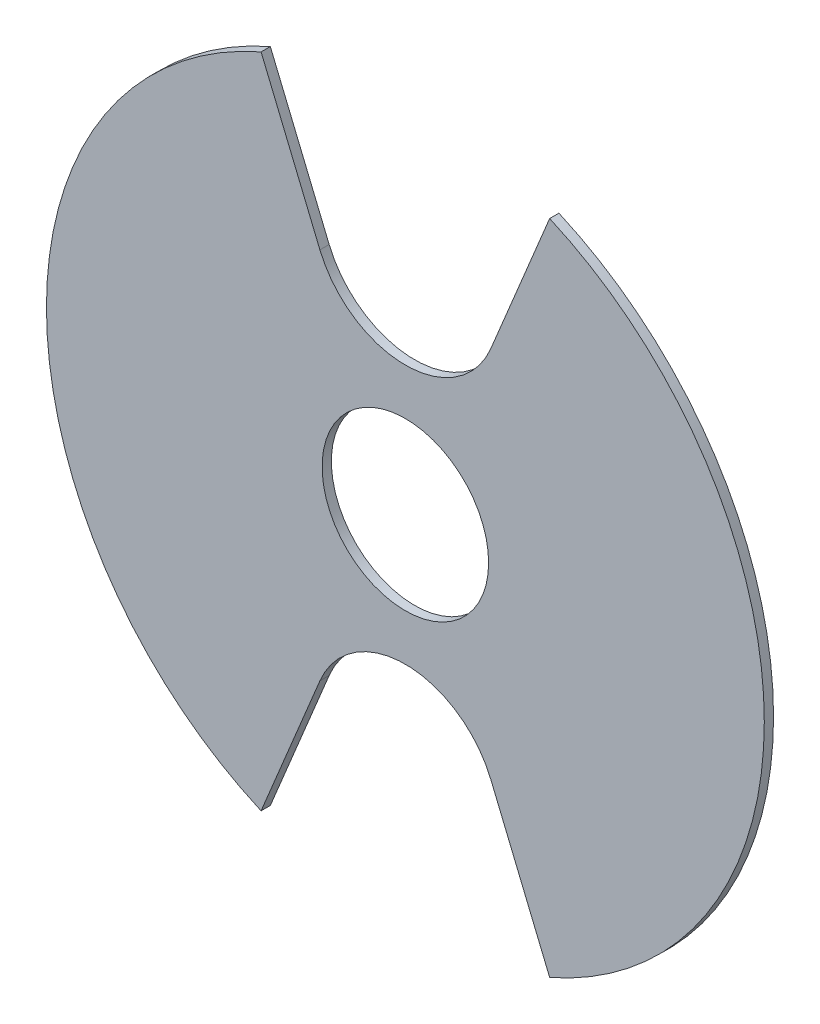
SolidWorks part; units mm, degrees
ref_plane "Front Plane" through (0, 0, 0) normal (0, 0, 1) x (1, 0, 0)
ref_plane "Top Plane" through (0, 0, 0) normal (0, 1, 0) x (1, 0, 0)
ref_plane "Right Plane" through (0, 0, 0) normal (1, 0, 0) x (0, 0, -1)
sketch "Esquisse1" plane through (0, 0, 0) normal (0, 0, 1) x (1, 0, 0)
  circle A0 centre (0, 0) radius 97
  circle A1 centre (0, 0) radius 22.5
  dimension "D1" = 194
  dimension "D2" = 45
extrude "Main" add sketch "Esquisse1" along normal blind 2.5
sketch "Esquisse2" plane through (0, 0, 2.5) normal (0, 0, 1) x (1, 0, 0)
  line L0 (-23.097, 50.4329) -> (-38.9959, 88.8162)
  line L1 (23.097, 50.4329) -> (38.9959, 88.8162)
  arc A0 (-23.097, 50.4329) -> (23.097, 50.4329) centre (0, 60) ccw
  circle A1 centre (0, 0) radius 97 construction
  dimension "D2" = 25
  dimension "D1" = 45
  dimension "D3" = 60
extrude "Enlèv. mat.-Extru.1" cut sketch "Esquisse2" against normal through all and the other way through all
mirror "Symétrie1" about plane through (0, 0, 0) normal (0, 1, 0) of "Enlèv. mat.-Extru.1"
